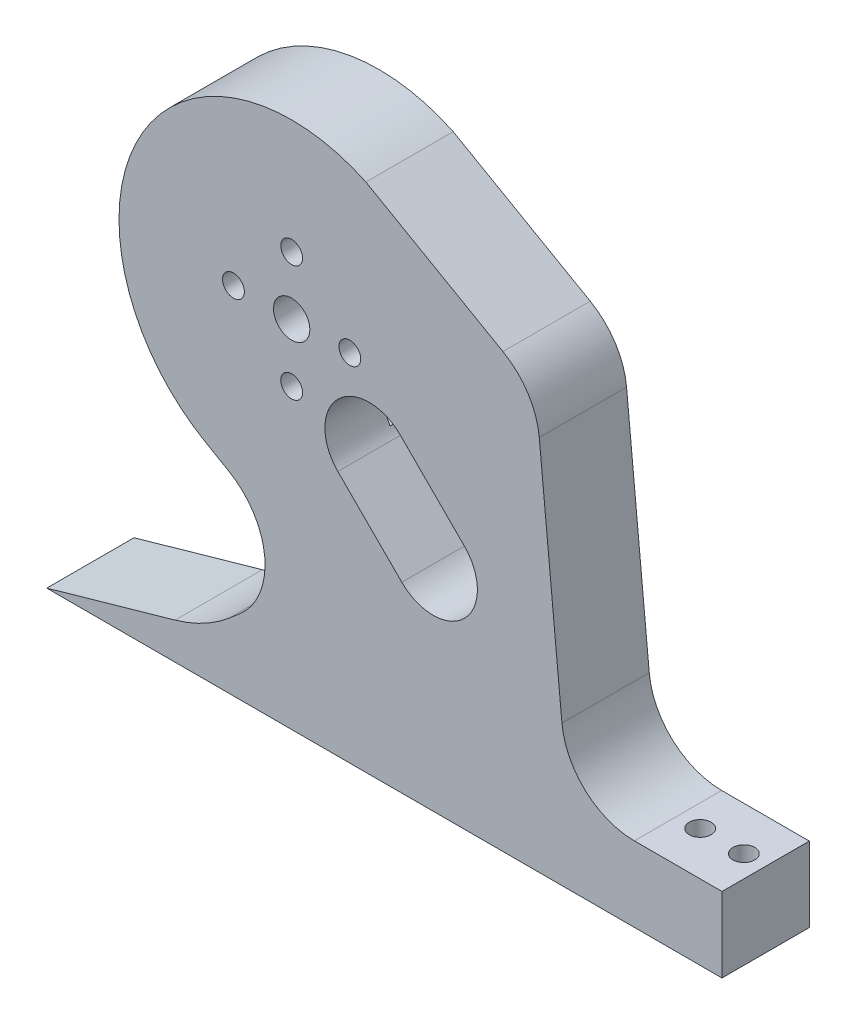
SolidWorks part; units mm, degrees
ref_plane "Front Plane" through (0, 0, 0) normal (0, 0, 1) x (1, 0, 0)
ref_plane "Top Plane" through (0, 0, 0) normal (0, 1, 0) x (1, 0, 0)
ref_plane "Right Plane" through (0, 0, 0) normal (1, 0, 0) x (0, 0, -1)
sketch "Sketch1" plane through (0, 0, 0) normal (0, 0, 1) x (1, 0, 0)
  line L0 (-3.1165, 51.7901) -> (-1.6309, 36.3244)
  line L4 (-8.1116, 59.5177) -> (-33.5078, 19.3458)
  line L5 (-26.9509, 70.2764) -> (-8.1116, 59.5177)
  line L6 (-1.6309, 36.3244) -> (0, 19.3458)
  line L7 (9.9542, 10.3019) -> (22, 10.3019)
  line L9 (-49.0189, 28.3011) -> (-33.5078, 19.3458)
  line L10 (-33.5078, 19.3458) -> (0, 0)
  line L11 (22, 10.3019) -> (22, 0)
  line L12 (22, 0) -> (0, 0)
  line L13 (0, 0) -> (-70.8223, 0)
  line L14 (-33.5078, 19.3458) -> (-45.7172, 8.9956)
  line L15 (-53.1824, 5.0134) -> (-70.8223, 0)
  arc A1 (-49.0189, 28.3011) -> (-26.9509, 70.2764) centre (-37.1539, 48.8518) cw
  arc A2 (0, 19.3458) -> (9.9542, 10.3019) centre (9.9542, 20.3019) ccw
  arc A3 (-3.1165, 51.7901) -> (-8.1116, 59.5177) centre (-13.0707, 50.8339) ccw
  arc A6 (-45.7172, 8.9956) -> (-53.1824, 5.0134) centre (-58.65, 24.2515) cw
  dimension "D3" = 23.73
  dimension "D6" = 10
  dimension "D7" = 10
  dimension "D8" = 12.0458
  dimension "D12" = 20
  dimension "D1" = 49.0189
  dimension "D2" = 22
  dimension "D4" = 10.3019
  dimension "D5" = 21.6949
  dimension "D11" = 70.8223
extrude "Boss-Extrude2" add sketch "Sketch1" against normal blind 12 contours L10 L12 L11 L7 A2 L6 L0 A3 L4
extrude "Boss-Extrude3" add sketch "Sketch1<8>" against normal blind 12 separate body contours L4 L9 A1 L5
sketch "Sketch1<8>" plane through (0, 0, 0) normal (0, 0, 1) x (1, 0, 0) same geometry as "Sketch1"
extrude "Boss-Extrude5" add sketch "Sketch1<10>" against normal up to surface (12 mm away) contours L15 L13 L10 L14 A6 up to face at (1.0515, 21.1611, -12)
sketch "Sketch1<10>" plane through (0, 0, 0) normal (0, 0, 1) x (1, 0, 0) same geometry as "Sketch1"
sketch "Sketch14" plane through (0, 0, -12) normal (0, 0, -1) x (-1, 0, 0)
  circle A0 centre (37.1539, 48.8518) radius 15
  dimension "D1" = 30
extrude "Cut-Extrude5" cut sketch "Sketch14" against normal blind 4
sketch "Sketch16" plane through (0, 0, -8) normal (0, 0, -1) x (-1, 0, 0)
  circle A0 centre (37.1539, 48.8518) radius 2.5
extrude "Cut-Extrude7" cut sketch "Sketch16" against normal up to surface (8 mm away) up to face at (-21.4366, 24.3401, 0)
sketch "Sketch15" plane through (0, 0, -8) normal (0, 0, -1) x (-1, 0, 0)
  circle A0 centre (37.1539, 56.8518) radius 1.5
  circle A1 centre (45.1539, 48.8518) radius 1.5
  circle A2 centre (37.1539, 40.8518) radius 1.5
  circle A3 centre (29.1539, 48.8518) radius 1.5
  point P3 (37.1539, 48.8518)
  point P13 (37.1539, 48.8518)
  dimension "D1" = 3
  dimension "D2" = 8
  dimension "D3" = 4
extrude "Cut-Extrude6" cut sketch "Sketch15" against normal up to surface (8 mm away) up to face at (-34.6539, 48.8518, 0)
sketch "Sketch19" plane through (0, 10.3019, 0) normal (0, 1, 0) x (1, 0, 0)
  line L0 (22, 12) -> (22, 0) construction
  line L1 (22, 0) -> (0, 0) construction
  line L2 (19, 6) -> (13, 6) construction
  circle A0 centre (19, 6) radius 1.5
  circle A1 centre (13, 6) radius 1.5
  dimension "D1" = 3
  dimension "D2" = 6
  dimension "D3" = 3
extrude "Cut-Extrude9" cut sketch "Sketch19" against normal up to surface (10.3019 mm away) up to face at (-24.4112, 0, -6)
sketch "Sketch20" plane through (0, 0, 0) normal (0, 0, 1) x (1, 0, 0)
  line L0 (-37.1539, 48.8518) -> (-17.7084, 29.4064) construction
  line L1 (-17.7084, 29.4064) -> (-26.5023, 38.2003) construction
  line L2 (-22.0106, 25.1042) -> (-30.8045, 33.8981)
  line L3 (-13.4062, 33.7086) -> (-22.2001, 42.5025)
  arc A0 (-22.0106, 25.1042) -> (-13.4062, 33.7086) centre (-17.7084, 29.4064) ccw
  arc A1 (-22.2001, 42.5025) -> (-30.8045, 33.8981) centre (-26.5023, 38.2003) ccw
  point P2 (-22.1054, 33.8033)
  dimension "D2" = 12.4364
  dimension "D3" = 6.0842
  dimension "D1" = 27.5
extrude "Cut-Extrude10" cut sketch "Sketch20" against normal up to surface (12 mm away) up to face at (-52.1539, 48.8518, -12)
fillet "Fillet1" radius 10 1 edges at (-33.5078, 19.3458, -6)
